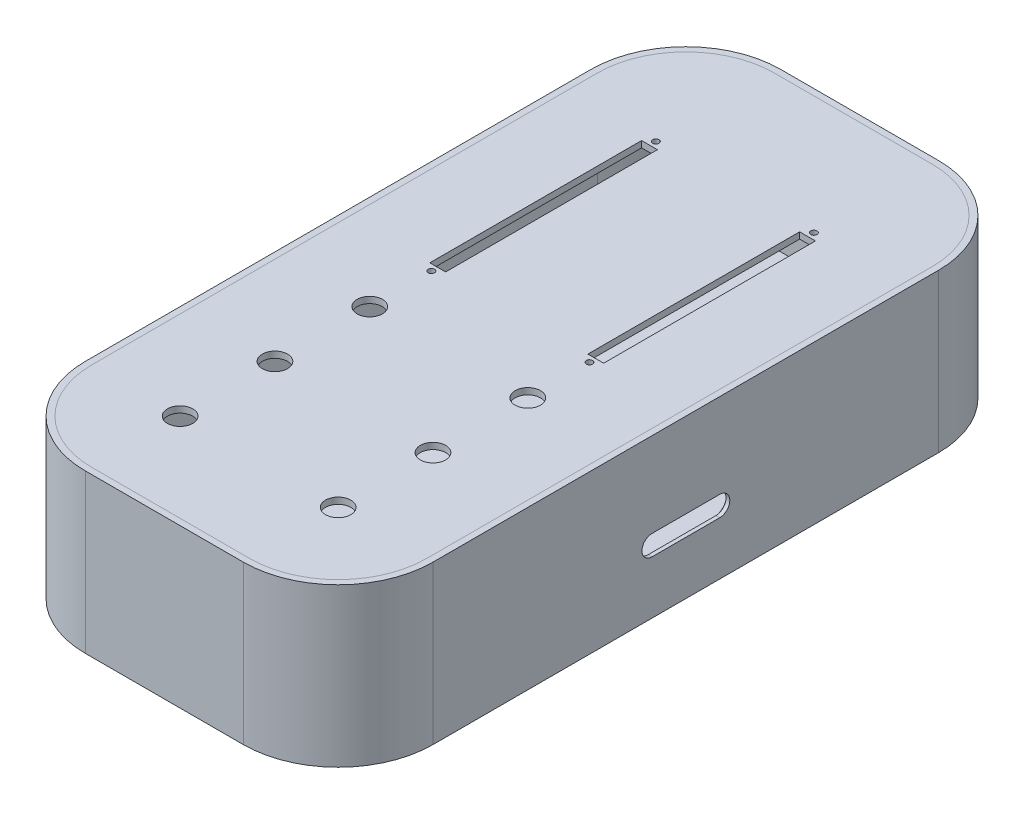
SolidWorks part; units mm, degrees
ref_plane "Front Plane" through (0, 0, 0) normal (0, 0, 1) x (1, 0, 0)
ref_plane "Top Plane" through (0, 0, 0) normal (0, 1, 0) x (1, 0, 0)
ref_plane "Right Plane" through (0, 0, 0) normal (1, 0, 0) x (0, 0, -1)
sketch "Sketch1" plane through (0, 0, 0) normal (0, 1, 0) x (1, 0, 0)
  line L0 (-53, -80) -> (-53, 80)
  line L1 (-25, -110) -> (25, -110)
  line L2 (-55, -80) -> (-55, 80)
  line L3 (-25, 110) -> (25, 110)
  line L4 (55, -80) -> (55, 80)
  line L5 (-55, -110) -> (55, 110) construction
  line L6 (-55, 110) -> (55, -110) construction
  line L7 (-25, 108) -> (25, 108)
  line L8 (53, -80) -> (53, 80)
  line L9 (-25, -108) -> (25, -108)
  arc A0 (-55, -80) -> (-25, -110) centre (-25, -80) ccw
  arc A1 (55, -80) -> (25, -110) centre (25, -80) cw
  arc A2 (55, 80) -> (25, 110) centre (25, 80) ccw
  arc A3 (-55, 80) -> (-25, 110) centre (-25, 80) cw
  arc A4 (-53, 80) -> (-25, 108) centre (-25, 80) cw
  arc A5 (53, 80) -> (25, 108) centre (25, 80) ccw
  arc A6 (53, -80) -> (25, -108) centre (25, -80) cw
  arc A7 (-53, -80) -> (-25, -108) centre (-25, -80) ccw
  point P0 (0, 0)
  dimension "D3" = 30
  dimension "D1" = 220
  dimension "D2" = 110
  dimension "D4" = 2
extrude "Boss-Extrude1" add sketch "Sketch1" along normal blind 50 contours L2 A3 L3 A2 L4 A1 L1 A0
shell "Shell1" thickness 2 removed face at (0, 50, 0)
sketch "Sketch2" plane through (0, 2, 0) normal (0, 1, 0) x (1, 0, 0)
  line L23 (-25, -102) -> (25, -102)
  line L24 (47, -80) -> (47, 80)
  line L25 (25, 102) -> (-25, 102)
  line L26 (-47, 80) -> (-47, -80)
  line L27 (-25, -102) -> (25, -102)
  line L28 (47, -80) -> (47, 80)
  line L29 (25, 102) -> (-25, 102)
  line L30 (-47, 80) -> (-47, -80)
  arc A21 (25, -102) -> (47, -80) centre (25, -80) ccw
  arc A22 (-47, -80) -> (-25, -102) centre (-25, -80) ccw
  arc A23 (47, 80) -> (25, 102) centre (25, 80) ccw
  arc A24 (-25, 102) -> (-47, 80) centre (-25, 80) ccw
  arc A25 (25, -102) -> (47, -80) centre (25, -80) ccw
  arc A26 (-47, -80) -> (-25, -102) centre (-25, -80) ccw
  arc A27 (47, 80) -> (25, 102) centre (25, 80) ccw
  arc A28 (-25, 102) -> (-47, 80) centre (-25, 80) ccw
  arc M9 (-53, -80) -> (-25, -108) centre (-25, -80) ccw
  line M10 (-25, -108) -> (25, -108)
  arc M11 (25, -108) -> (53, -80) centre (25, -80) ccw
  line M12 (53, -80) -> (53, 80)
  arc M13 (53, 80) -> (25, 108) centre (25, 80) ccw
  line M14 (25, 108) -> (-25, 108)
  arc M15 (-25, 108) -> (-53, 80) centre (-25, 80) ccw
  line M16 (-53, 80) -> (-53, -80)
  dimension "D1" = 6
extrude "Boss-Extrude2" add sketch "Sketch2" along normal blind 2 from offset 44 contours A28 L29 A27 L28 A25 L27 A26 L30 M16 M9 M10 M11 M12 M13 M14 M15 region at (-50.5939, 2, 0)
extrude "Boss-Extrude3" add sketch "Sketch1<3>" along normal blind 2 from surface separate body contours L0 A4 L7 A5 L8 A6 L9 A7 starting at face at (0, 48, 0)
sketch "Sketch1<3>" plane through (0, 0, 0) normal (0, 1, 0) x (1, 0, 0) same geometry as "Sketch1"
sketch "Sketch3" plane through (0, 48, 0) normal (0, -1, 0) x (1, 0, 0)
  line L0 (53, 80) -> (53, -80) construction
  line L1 (-53, 80) -> (-53, -80) construction
  line L3 (-27.5, -68.5) -> (-22.5, -68.5)
  line L4 (-27.5, -68.5) -> (-27.5, -1.5)
  line L5 (-27.5, -1.5) -> (-22.5, -1.5)
  line L6 (-22.5, -68.5) -> (-22.5, -1.5)
  line L7 (-27.5, -68.5) -> (-22.5, -1.5) construction
  line L8 (-27.5, -1.5) -> (-22.5, -68.5) construction
  line L9 (27.5, -68.5) -> (22.5, -68.5)
  line L10 (27.5, -68.5) -> (27.5, -1.5)
  line L11 (27.5, -1.5) -> (22.5, -1.5)
  line L12 (22.5, -68.5) -> (22.5, -1.5)
  line L13 (27.5, -68.5) -> (22.5, -1.5) construction
  line L14 (27.5, -1.5) -> (22.5, -68.5) construction
  circle A0 centre (-25, 80) radius 4
  circle A1 centre (25, 80) radius 4
  circle A2 centre (-25, 50) radius 4
  circle A3 centre (25, 50) radius 4
  circle A4 centre (-25, 20) radius 4
  circle A5 centre (25, 20) radius 4
  circle A6 centre (-25, 0.5) radius 1
  circle A7 centre (25, 0.5) radius 1
  circle A8 centre (25, -70.5) radius 1
  circle A9 centre (-25, -70.5) radius 1
  point P18 (-25, -35)
  point P23 (25, -35)
  dimension "D1" = 8
  dimension "D2" = 8
  dimension "D3" = 8
  dimension "D4" = 8
  dimension "D5" = 8
  dimension "D6" = 8
  dimension "D19" = 2
  dimension "D20" = 2
  dimension "D21" = 2
  dimension "D22" = 2
  dimension "D24" = 2
  dimension "D7" = 30
  dimension "D8" = 28
  dimension "D9" = 30
  dimension "D10" = 28
  dimension "D11" = 30
  dimension "D12" = 30
  dimension "D13" = 28
  dimension "D14" = 28
  dimension "D15" = 5
  dimension "D16" = 5
  dimension "D17" = 28
  dimension "D18" = 28
  dimension "D23" = 2
  dimension "D25" = 2
  dimension "D26" = 2
  dimension "D27" = 71
  dimension "D28" = 71
  dimension "D29" = 55
  dimension "D30" = 55
  dimension "D31" = 67
  dimension "D32" = 67
  dimension "D33" = 28
  dimension "D34" = 28
extrude "Cut-Extrude1" cut sketch "Sketch3" against normal up to next (2 mm away)
sketch "Sketch4" plane through (55, 0, 0) normal (1, 0, 0) x (0, 0, -1)
  line L0 (-10.7, 20) -> (10.7, 20) construction
  line L1 (-10.7, 23.2) -> (10.7, 23.2)
  line L2 (-10.7, 16.8) -> (10.7, 16.8)
  line L3 (-110, 50) -> (-110, 0) construction
  line L4 (-10.7, 20) -> (10.7, 20) construction
  line L5 (-10.7, 24.2) -> (10.7, 24.2)
  line L6 (-10.7, 15.8) -> (10.7, 15.8)
  arc A0 (-10.7, 23.2) -> (-10.7, 16.8) centre (-10.7, 20) ccw
  arc A1 (10.7, 16.8) -> (10.7, 23.2) centre (10.7, 20) ccw
  arc A2 (-10.7, 24.2) -> (-10.7, 15.8) centre (-10.7, 20) ccw
  arc A3 (10.7, 15.8) -> (10.7, 24.2) centre (10.7, 20) ccw
  point P2 (0, 20)
  point P10 (-13.9, 20)
  point P11 (13.9, 20)
  point P14 (0, 20)
  dimension "D1" = 110
  dimension "D2" = 20
  dimension "D3" = 6.4
  dimension "D4" = 27.8
  dimension "D5" = 8.4
extrude "Cut-Extrude2" cut sketch "Sketch4" against normal up to next (2 mm away) contours L2 A1 L1 A0 region at (55, 20, 0)
extrude "Cut-Extrude3" cut sketch "Sketch4<4>" against normal up to next (2 mm away) from offset 1.2 offset against normal yes
sketch "Sketch4<4>" plane through (55, 0, 0) normal (1, 0, 0) x (0, 0, -1) same geometry as "Sketch4"
